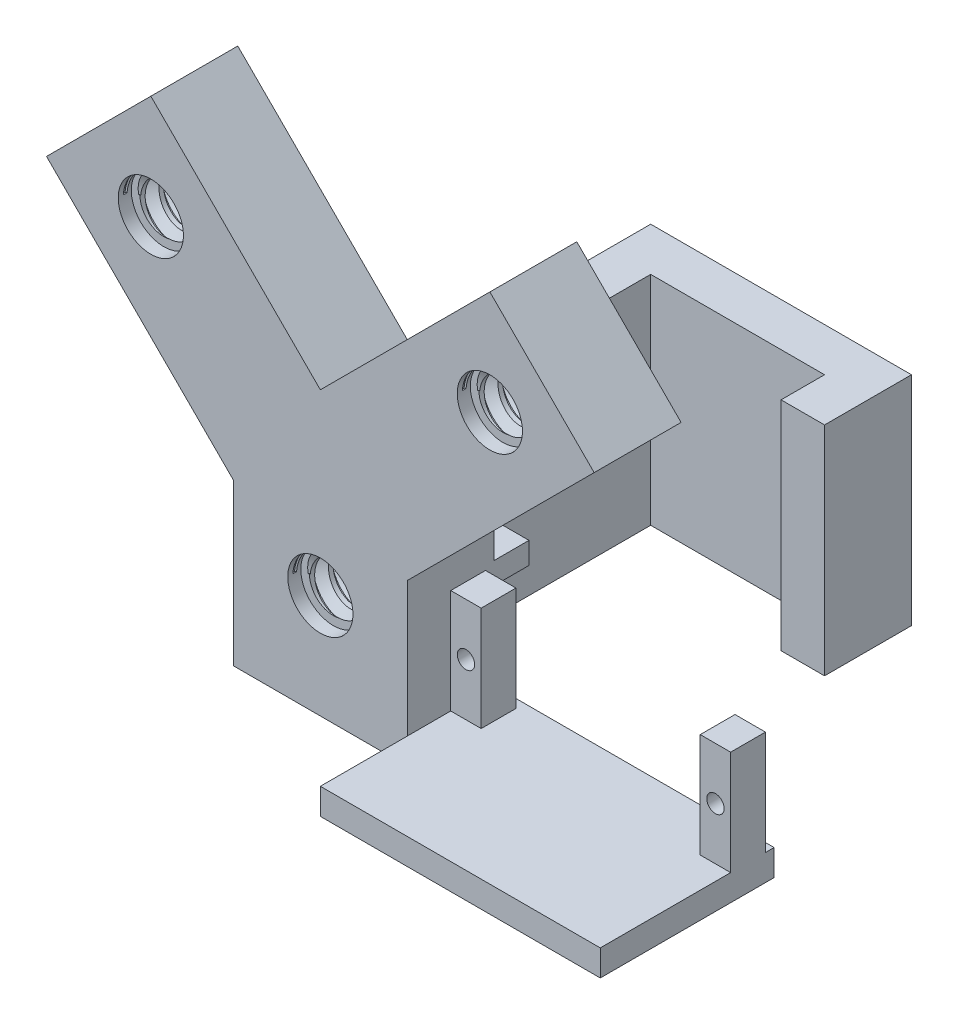
SolidWorks part; units mm, degrees
ref_plane "Front Plane" through (0, 0, 0) normal (0, 0, 1) x (1, 0, 0)
ref_plane "Top Plane" through (0, 0, 0) normal (0, 1, 0) x (1, 0, 0)
ref_plane "Right Plane" through (0, 0, 0) normal (1, 0, 0) x (0, 0, -1)
sketch "Sketch1" plane through (0, 0, 0) normal (0, 0, 1) x (1, 0, 0)
  line L0 (-31.5, 0) -> (-31.5, -80.9035) construction
  line L1 (0, 0) -> (-63, 0)
  line L2 (0, 0) -> (0, -52)
  line L3 (0, -52) -> (-63, -52)
  line L4 (-63, 0) -> (-63, -52)
  line L5 (-63, -12) -> (-51, 0)
  line L6 (-51, 0) -> (-31.5, -19.5)
  line L8 (-21.5, -52) -> (-41.5, -52)
  line L9 (-41.5, -52) -> (-41.5, -33.5)
  line L10 (-41.5, -33.5) -> (-63, -12)
  line L11 (-21.5, -52) -> (-21.5, -33.5)
  line L12 (-12, 0) -> (-31.5, -19.5)
  line L13 (0, -12) -> (-12, 0)
  line L14 (-21.5, -33.5) -> (0, -12)
  circle A0 centre (-51, -12) radius 2.75
  circle A1 centre (-12, -12) radius 2.75
  circle A2 centre (-31.5, -40) radius 2.75
  point P11 (-31.5, -52)
  dimension "D2" = 12
  dimension "D3" = 28
  dimension "D4" = 0
  dimension "D6" = 0
  dimension "D7" = 39
  dimension "D8" = 12
  dimension "D9" = 5.5
  dimension "D10" = 5.5
  dimension "D14" = 12
  dimension "D16" = 10
  dimension "D15" = 12
  dimension "D17" = 5.5
  dimension "D1" = 63
  dimension "D5" = 12
  dimension "D11" = 90
  dimension "D12" = 90
  dimension "D13" = 12
extrude "Boss-Extrude1" add sketch "Sketch1" along normal blind 10 contours L0 L6 L5 L10 L9 L8 A2 A0 | L12 L0 A2 L3 L11 L14 L13 A1 region at (-19.9332, -24.1984, 0) region at (-43.0668, -24.1984, 0)
thread "Thread1" pitch 2.1167 method cut profile "Thread Profile1" start angle 0, offset 0, length 20, pitch 2.1167, diameter 5.5
ref_plane "Plane1" through (-53.75, -12, 10) normal (0, -1, 0) x (-1, 0, 0)
sketch "Thread Profile1" plane through (-53.75, -12, 10) normal (0, -1, 0) x (-1, 0, 0)
  line L0 (0, 0) -> (0, 2.1167) construction
  line L1 (0, 0) -> (1.1457, 0.6615)
  line L2 (1.1457, 0.6615) -> (1.1457, 0.926)
  line L3 (1.1457, 0.926) -> (0, 1.5875)
  line L4 (1.1457, 0.7937) -> (0, 0.7937) construction
  line L11 (0, 0) -> (0, 1.5875)
  point P2 (0, 0)
  dimension "Pitch" = 2.1167
  dimension "Profile_Angle" = 60
  dimension "Profile_Land" = 0.2646
  dimension "Profile_Height" = 1.1457
thread "Thread2" pitch 2.1167 method cut profile "Thread Profile2" start angle 0, offset 0, length 20, pitch 2.1167, diameter 5.5
ref_plane "Plane2" through (-14.75, -12, 10) normal (0, -1, 0) x (-1, 0, 0)
sketch "Thread Profile2" plane through (-14.75, -12, 10) normal (0, -1, 0) x (-1, 0, 0)
  line L0 (0, 0) -> (0, 2.1167) construction
  line L1 (0, 0) -> (1.1457, 0.6615)
  line L2 (1.1457, 0.6615) -> (1.1457, 0.926)
  line L3 (1.1457, 0.926) -> (0, 1.5875)
  line L4 (1.1457, 0.7937) -> (0, 0.7937) construction
  line L11 (0, 0) -> (0, 1.5875)
  point P2 (0, 0)
  dimension "Pitch" = 2.1167
  dimension "Profile_Angle" = 60
  dimension "Profile_Land" = 0.2646
  dimension "Profile_Height" = 1.1457
thread "Thread3" pitch 2.1167 method cut profile "Thread Profile3" start angle 0, offset 0, length 20, pitch 2.1167, diameter 5.5
ref_plane "Plane3" through (-34.25, -40, 10) normal (0, -1, 0) x (-1, 0, 0)
sketch "Thread Profile3" plane through (-34.25, -40, 10) normal (0, -1, 0) x (-1, 0, 0)
  line L0 (0, 0) -> (0, 2.1167) construction
  line L1 (0, 0) -> (1.1457, 0.6615)
  line L2 (1.1457, 0.6615) -> (1.1457, 0.926)
  line L3 (1.1457, 0.926) -> (0, 1.5875)
  line L4 (1.1457, 0.7937) -> (0, 0.7937) construction
  line L11 (0, 0) -> (0, 1.5875)
  point P2 (0, 0)
  dimension "Pitch" = 2.1167
  dimension "Profile_Angle" = 60
  dimension "Profile_Land" = 0.2646
  dimension "Profile_Height" = 1.1457
sketch "Sketch8" plane through (0, 0, 10) normal (0, 0, 1) x (1, 0, 0)
  circle A0 centre (-51, -12) radius 3.75
  circle A1 centre (-12, -12) radius 3.75
  circle A2 centre (-31.5, -40) radius 3.75
  dimension "D1" = 7.5
  dimension "D2" = 7.5
  dimension "D3" = 7.5
extrude "Cut-Extrude2" cut sketch "Sketch8" against normal blind 1.5
sketch "Sketch9" plane through (-21.5, 0, 0) normal (1, 0, 0) x (0, 0, -1)
  line L1 (0, -52) -> (-20, -52)
  line L2 (0, -52) -> (0, -49)
  line L3 (0, -49) -> (-20, -49)
  line L4 (-20, -52) -> (-20, -49)
  line L5 (-10, -52) -> (-10, -33.5) construction
  dimension "D1" = 3
  dimension "D2" = 10
extrude "Boss-Extrude3" add sketch "Sketch9" along normal blind 32.2
sketch "Sketch10" plane through (0, -49, 0) normal (0, 1, 0) x (1, 0, 0)
  line L0 (-21.5, 0) -> (-21.5, -10) construction
  line L1 (-21.5, -1) -> (-18, -1)
  line L2 (-21.5, -1) -> (-21.5, -5)
  line L3 (-21.5, -5) -> (-18, -5)
  line L4 (-18, -1) -> (-18, -5)
  line L5 (-5.4, -20) -> (-5.4, 7.6272) construction
  line L6 (10.7, -20) -> (-21.5, -20) construction
  line L7 (10.7, 0) -> (-21.5, 0) construction
  line L8 (10.7, -5) -> (7.2, -5)
  line L9 (7.2, -1) -> (7.2, -5)
  line L10 (10.7, -1) -> (7.2, -1)
  line L11 (10.7, -1) -> (10.7, -5)
  dimension "D1" = 4
  dimension "D2" = 1
  dimension "D3" = 3.5
extrude "Boss-Extrude4" add sketch "Sketch10" along normal blind 12
sketch "Sketch11" plane through (0, 0, 1) normal (0, 0, -1) x (-1, 0, 0)
  line L0 (18, -37) -> (18, -49) construction
  line L1 (-7.2, -37) -> (-7.2, -49) construction
  line L2 (18, -37) -> (21.5, -37) construction
  line L3 (-10.7, -37) -> (-7.2, -37) construction
  circle A0 centre (-8.95, -43) radius 1
  circle A1 centre (19.75, -43) radius 1
  point P6 (18, -43)
  point P9 (-7.2, -43)
  point P12 (19.75, -37)
  point P15 (-8.95, -37)
  dimension "D1" = 0
  dimension "D2" = 0
  dimension "D3" = 2
  dimension "D4" = 2
  dimension "D5" = 0
  dimension "D6" = 0
extrude "Cut-Extrude3" cut sketch "Sketch11" against normal blind 22
sketch "Sketch13" plane through (0, -52, 0) normal (0, -1, 0) x (-1, 0, 0)
  line L0 (36.5, 0) -> (36.5, 33)
  line L1 (36.5, 33) -> (6.5, 33)
  line L2 (6.5, 33) -> (6.5, 23)
  line L3 (6.5, 23) -> (11.5, 23)
  line L4 (11.5, 23) -> (11.5, 28)
  line L5 (11.5, 28) -> (31.5, 28)
  line L6 (31.5, 28) -> (31.5, 0)
  line L7 (-10.7, 0) -> (41.5, 0) construction
  line L8 (31.5, 0) -> (36.5, 0)
  dimension "D1" = 10
  dimension "D2" = 5
  dimension "D3" = 28
  dimension "D4" = 20
  dimension "D5" = 30
  dimension "D6" = 10
  dimension "D7" = 5
extrude "Boss-Extrude5" add sketch "Sketch13" against normal blind 25
sketch "Sketch14" plane through (0, 0, 0) normal (0, 0, -1) x (-1, 0, 0)
  line L0 (21.5, -49) -> (21.5, -33.5) construction
  line L1 (21.5, -39) -> (31.5, -39)
  line L2 (21.5, -39) -> (21.5, -36.5)
  line L3 (21.5, -36.5) -> (31.5, -36.5)
  line L4 (31.5, -39) -> (31.5, -36.5)
  line L5 (31.5, -42.75) -> (31.5, -52) construction
  line L6 (-10.7, -49) -> (21.5, -49) construction
  dimension "D1" = 2.5
  dimension "D2" = 10
extrude "Boss-Extrude6" add sketch "Sketch14" along normal blind 4
sketch "Sketch15" plane through (0, 0, 0) normal (0, 0, -1) x (-1, 0, 0)
  line L0 (41.5, -52) -> (41.5, -33.5) construction
  line L1 (41.5, -43) -> (39, -43)
  line L2 (41.5, -43) -> (41.5, -46)
  line L3 (41.5, -46) -> (39, -46)
  line L4 (39, -43) -> (39, -46)
  line L6 (36.5, -52) -> (41.5, -52) construction
  line L7 (36.5, -27) -> (36.5, -52) construction
  point P10 (0, 0)
  dimension "D1" = 6
  dimension "D2" = 3
  dimension "D3" = 2.5
extrude "Boss-Extrude7" add sketch "Sketch15" along normal blind 7
sketch "Sketch16" plane through (0, -46, 0) normal (0, -1, 0) x (-1, 0, 0)
  line L1 (41.5, 7) -> (39, 7)
  line L2 (41.5, 7) -> (41.5, 3.5)
  line L3 (41.5, 3.5) -> (39, 3.5)
  line L4 (39, 7) -> (39, 3.5)
  line L5 (39, 7) -> (41.5, 7) construction
  line L6 (39, 7) -> (39, 0) construction
  line L7 (41.5, 7) -> (41.5, 0) construction
  point P11 (0, 0)
  point P12 (39, 3.5)
  dimension "D1" = 0
  dimension "D2" = 3.5
  dimension "D3" = 0
  dimension "D4" = 0
  dimension "D5" = 90
extrude "Boss-Extrude8" add sketch "Sketch16" along normal up to vertex (6 mm away) up to point (-36.5, -52, 0)
